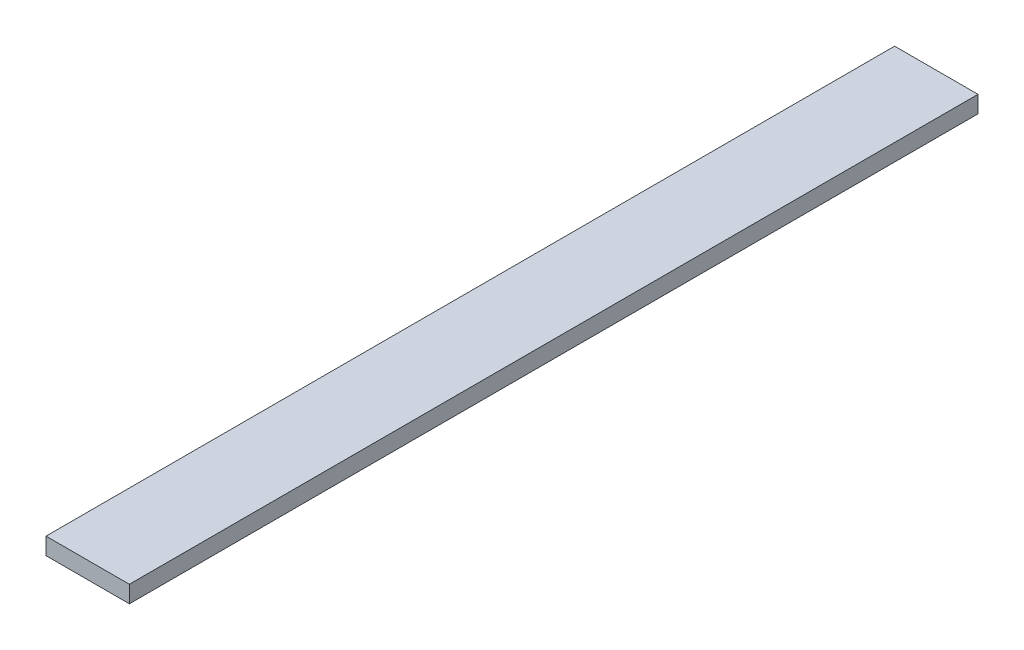
SolidWorks part; units mm, degrees
ref_plane "Front Plane" through (0, 0, 0) normal (0, 0, 1) x (1, 0, 0)
ref_plane "Top Plane" through (0, 0, 0) normal (0, 1, 0) x (1, 0, 0)
ref_plane "Right Plane" through (0, 0, 0) normal (1, 0, 0) x (0, 0, -1)
sketch "Sketch2" plane through (0, 0, 0) normal (0, 1, 0) x (1, 0, 0)
  line L0 (2.46, -25.04) -> (2.46, 25.04)
  line L1 (-2.46, -25.04) -> (-2.46, 25.04)
  line L2 (2.46, -25.04) -> (-2.46, -25.04)
  line L3 (2.46, 25.04) -> (-2.46, 25.04)
  line L4 (2.46, 25.04) -> (-2.46, -25.04) construction
  line L5 (-2.46, 25.04) -> (2.46, -25.04) construction
  point P2 (0, -25.04)
  point P5 (0, 25.04)
  point P6 (0, 0)
  dimension "D1" = 50.08
  dimension "D2" = 4.92
extrude "Boss-Extrude1" add sketch "Sketch2" along normal mid plane 1
